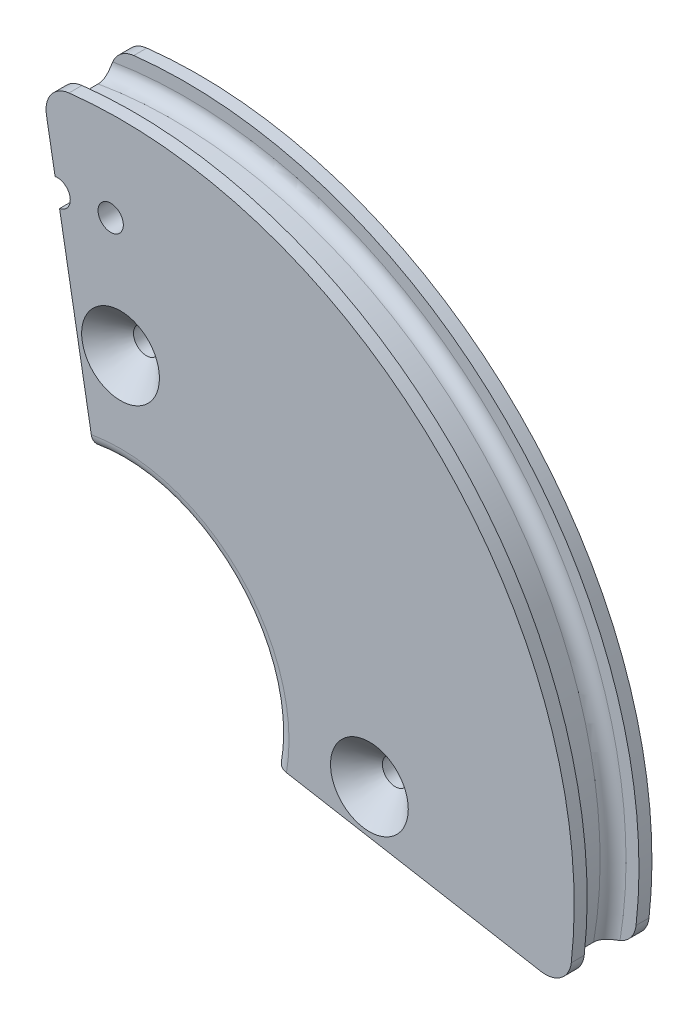
SolidWorks part; units mm, degrees
ref_plane "Front" through (0, 0, 0) normal (0, 0, 1) x (1, 0, 0)
ref_plane "Top" through (0, 0, 0) normal (0, 1, 0) x (1, 0, 0)
ref_plane "Right" through (0, 0, 0) normal (1, 0, 0) x (0, 0, -1)
sketch "Sketch1" plane through (0, 0, 0) normal (0, 0, 1) x (1, 0, 0)
  circle A2 centre (9.6, 0) radius 0.5
  circle A24 centre (0, 0) radius 17
  circle A25 centre (0, 0) radius 6
  circle A30 centre (0, -9.6) radius 0.5
  circle A32 centre (-9.6, 0) radius 0.5
  circle A34 centre (0, 9.6) radius 0.5
  point P20 (0, 0)
  dimension "D1" = 4
  dimension "D2" = 34
  dimension "D3" = 12
extrude "Boss-Extrude1" add sketch "Sketch1" along normal mid plane 3
sketch "Sketch2" plane through (0, 0, 0) normal (0, 1, 0) x (1, 0, 0)
  line L1 (0, 0) -> (0, 3.24) construction
  line L2 (17, 0) -> (19.1765, -2.75) construction
  line L3 (17, -1.5) -> (17, 1.5) construction
  line L4 (-17, 0) -> (-16.5, 0) construction
  line L5 (-17, 1.5) -> (-17, -1.5) construction
  line L6 (-16.5, -0.5) -> (-16.5, 0.5)
  line L7 (-17, 1) -> (-17, -1)
  arc A1 (-16.5, 0.5) -> (-17, 1) centre (-17, 0.5) ccw
  arc A2 (-16.5, -0.5) -> (-17, -1) centre (-17, -0.5) cw
  dimension "D1" = 33
  dimension "D2" = 2
revolve "Cut-Revolve1" cut sketch "Sketch2" angle 360 about L1
sketch "Sketch3" plane through (0, 0, 1.5) normal (0, 0, 1) x (1, 0, 0)
  line L0 (-17, 0) -> (0, 0)
  line L3 (0, 0) -> (2.952, 16.7417)
  arc A1 (-17, 0) -> (2.952, 16.7417) centre (0, 0) cw
  circle A2 centre (0, 0) radius 6 construction
  circle A3 centre (0, 0) radius 17 construction
  dimension "D4" = 100
sketch "Sketch7" plane through (0, 0, 0) normal (0, 1, 0) x (1, 0, 0)
  line L0 (1.4542, 0) -> (0, 0) construction
  line L1 (17, 1.5) -> (17.5, 1.5)
  line L2 (17, 1.5) -> (17, 1)
  line L3 (17, 1) -> (17.5, 1)
  line L4 (17.5, 1.5) -> (17.5, 1)
  line L5 (0, 0) -> (0, 3.1931) construction
  line L6 (17.5, -1.5) -> (17.5, -1)
  line L7 (17, -1) -> (17.5, -1)
  line L8 (17, -1.5) -> (17, -1)
  line L9 (17, -1.5) -> (17.5, -1.5)
  dimension "D1" = 0.5
revolve "Revolve1" add sketch "Sketch7" angle 360 about L5
sketch "Sketch4" plane through (0, 0, 0) normal (0, 0, 1) x (1, 0, 0)
  line L0 (-3.309, 18.7662) -> (0, 0)
  line L1 (0, 0) -> (12.0208, 12.0208) construction
  line L2 (0, 0) -> (-16.6927, 0) construction
  line L3 (18.7662, -3.309) -> (0, 0)
  line L5 (-3.309, 18.7662) -> (-24.9321, 18.7662)
  line L6 (-24.9321, 18.7662) -> (-24.9321, -21.7847)
  line L7 (-24.9321, -21.7847) -> (18.7662, -21.7847)
  line L10 (18.7662, -3.309) -> (18.7662, -21.7847)
  line L11 (-3.309, 18.7662) -> (18.7662, -3.309) construction
  point P0 (7.7286, 7.7286)
  dimension "D1" = 135
  dimension "D2" = 110
extrude "Cut-Extrude1" cut sketch "Sketch4" against normal through all both and the other way through all
sketch "Sketch5" plane through (0, 0, 1.5) normal (0, 0, 1) x (1, 0, 0)
  line L1 (-1.0419, 5.9088) -> (-3.0388, 17.2341) construction
  circle A0 centre (-2.4395, 13.835) radius 0.5
  circle A1 centre (-0.3798, 14.0213) radius 0.4873
  dimension "D1" = 1
extrude "Cut-Extrude2" cut sketch "Sketch5" against normal through all both and the other way through all
fillet "Fillet1" radius 0.5 2 edges at (4.2426, 4.2426, 1.5) (4.2426, 4.2426, -1.5)
chamfer "Chamfer1" distance 1 angle 45 2 edges at (10.1, 0, 1.5) (0.5, 9.6, 1.5)
sketch "Sketch6" plane through (0, 0, -1.5) normal (0, 0, -1) x (-1, 0, 0)
  line L0 (0, 0) -> (-12.3744, 12.3744) construction
  line L1 (-12.3744, 12.3744) -> (1.3226, 15.1171)
  line L2 (1.3226, 15.1171) -> (0, 0)
  line L3 (-12.3744, 12.3744) -> (-15.1171, -1.3226)
  line L4 (-15.1171, -1.3226) -> (0, 0)
  arc A1 (3.0388, 17.2341) -> (-17.2341, -3.0388) centre (0, 0) ccw construction
  dimension "D1" = 50
fillet "Fillet2" radius 1 2 edges at (17.2341, -3.0388, 1.25) (-3.0388, 17.2341, -1.25)
